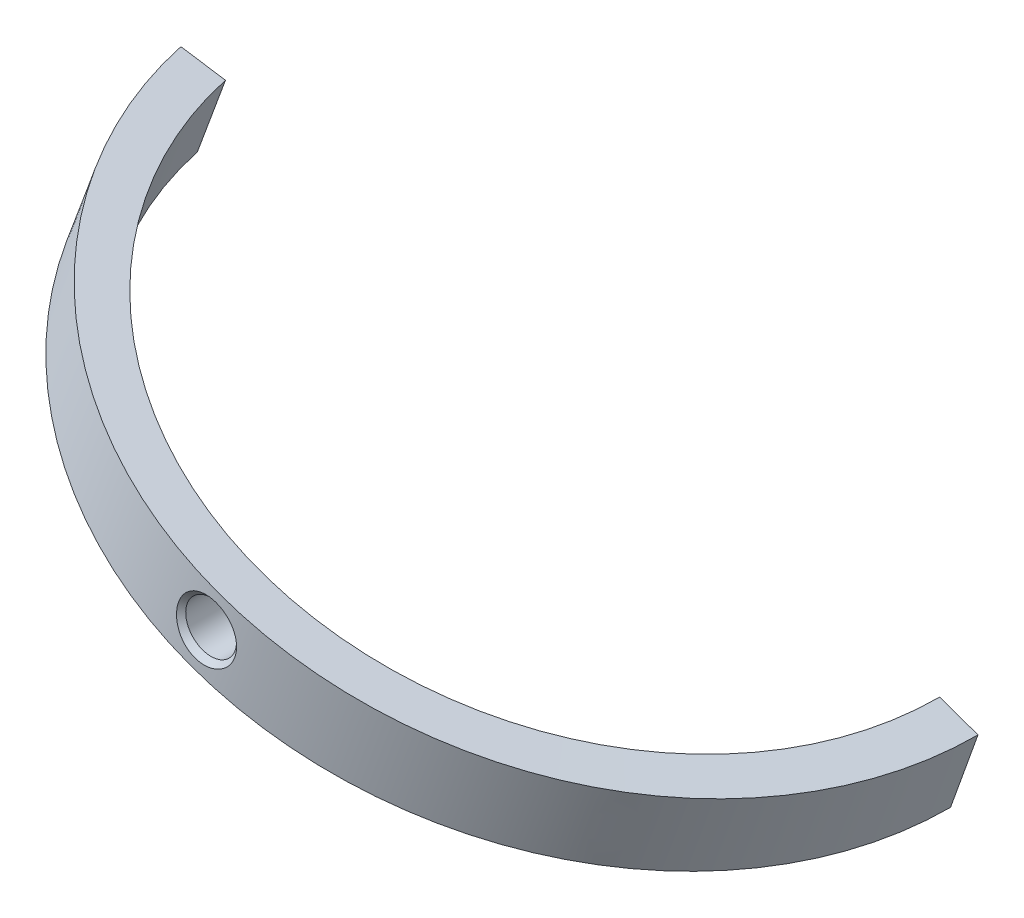
SolidWorks part; units mm, degrees
ref_plane "Přední rovina" through (0, 0, 0) normal (0, 0, 1) x (1, 0, 0)
ref_plane "Horní rovina" through (0, 0, 0) normal (0, 1, 0) x (1, 0, 0)
ref_plane "Pravá rovina" through (0, 0, 0) normal (1, 0, 0) x (0, 0, -1)
sketch "Skica1" plane through (0, 0, 0) normal (0, 0, 1) x (1, 0, 0)
  line L4 (-358.1756, -31.959) -> (-356.8238, -28.1944)
  line L6 (-358.1756, -31.959) -> (-355.8228, -32.804) construction
  line L7 (-356.8238, -28.1944) -> (-358.7061, -27.5185) construction
  line L8 (-356.4858, -27.2532) -> (-356.8238, -28.1944) construction
  line L9 (-358.7061, -27.5185) -> (-356.8238, -28.1944)
  line L10 (-360.058, -31.2831) -> (-358.7061, -27.5185)
  line L11 (-358.1756, -31.959) -> (-360.058, -31.2831)
  line L12 (-372.8806, -16.0194) -> (-374.7984, -21.2885) construction
  line L13 (-372.8806, -16.0194) -> (-374.7984, -21.2885) construction
  dimension "D2" = 2
revolve "Rotovat1" add sketch "Skica1" angle 170 about L13
hole_wizard "M3 závit1" positions "3DSkica2" profile "Skica4" tap size "M3" standard "ISO" end condition up to next
sketch3d "3DSkica2"
  line L7 (-376.2837, -25.3683, 19.2698) -> (-376.2866, -25.3764, 17.2698) construction
  line L12 (-376.2837, -25.3683, 19.2698) -> (-362.2644, -30.4708, 19.2701) construction
  line L15 (-360.058, -31.2831, 0) -> (-358.1756, -31.959, 0) construction
  line L16 (-376.2837, -25.3683, 19.2698) -> (-374.9156, -21.6095, 19.2526) construction
  arc A4 (-394.1159, -18.8778, 3.3462) -> (-358.1756, -31.959, 0) centre (-376.2833, -25.3684, 0) ccw construction
  arc A5 (-392.2681, -19.5596, 2.9989) -> (-360.058, -31.2831, 0) centre (-376.2863, -25.3765, 0) ccw construction
  arc A9 (-392.7319, -15.1249, 3.3432) -> (-356.8238, -28.1944, 0) centre (-374.9153, -21.6096, 0) ccw construction
  point P36 (-369.6927, -7.2607, 0)
  point P40 (-370.3797, -9.1482, 0)
  point P76 (-368.3305, -3.5182, 0)
  point P77 (-375.5996, -23.4889, 19.2612)
  point P80 (-375.5996, -23.4889, 19.2612)
  point P82 (-375.5996, -23.4889, 19.2612)
sketch "Skica4" plane through (-375.5996, -23.4889, 19.2612) normal (0.7071, 0.7071, -0.0039) x (0.7071, -0.7071, 0.0018)
  line L0 (0, 0) -> (0, 19.3179)
  line L1 (0, 19.3179) -> (1.25, 19.3179)
  line L2 (1.25, 19.3179) -> (1.25, 0.275)
  line L3 (1.25, 0.275) -> (1.525, 0)
  line L5 (1.525, 0) -> (0, 0)
  line L6 (-1.25, 0.275) -> (-1.525, 0) construction
  line L11 (0, -6.35) -> (0, 107.95) construction
  dimension "Průměr závitníku" = 2.5
  dimension "Hloubka závitníku" = 19.3179
  dimension "Průměr blíz. kuž. zahloubení" = 3.05
  dimension "Úhel blíz. kuž. zahloubení" = 90
cosmetic thread "Závit díry5" parameters "D2"=3
